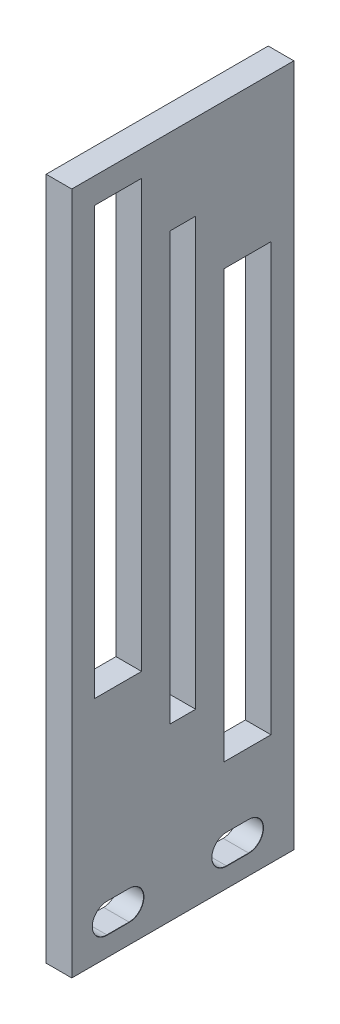
SolidWorks part; units mm, degrees
ref_plane "Front Plane" through (0, 0, 0) normal (0, 0, 1) x (1, 0, 0)
ref_plane "Top Plane" through (0, 0, 0) normal (0, 1, 0) x (1, 0, 0)
ref_plane "Right Plane" through (0, 0, 0) normal (1, 0, 0) x (0, 0, -1)
sketch "Sketch1" plane through (0, 0, 0) normal (1, 0, 0) x (0, 0, -1)
  line L1 (0, 0) -> (26, 0)
  line L2 (0, 0) -> (0, 80)
  line L3 (0, 80) -> (26, 80)
  line L4 (26, 0) -> (26, 80)
  dimension "D1" = 26
  dimension "D2" = 80
extrude "Boss-Extrude1" add sketch "Sketch1" along normal blind 3
sketch "Sketch2" plane through (3, 0, 0) normal (1, 0, 0) x (0, 0, -1)
  line L0 (26, 80) -> (0, 80) construction
  line L1 (2.675, 77) -> (8.175, 77)
  line L2 (2.675, 77) -> (2.675, 27)
  line L3 (2.675, 27) -> (8.175, 27)
  line L4 (8.175, 77) -> (8.175, 27)
  line L5 (11.5, 70) -> (14.5, 70)
  line L6 (11.5, 70) -> (11.5, 20)
  line L7 (11.5, 20) -> (14.5, 20)
  line L8 (14.5, 70) -> (14.5, 20)
  line L9 (17.825, 63) -> (23.325, 63)
  line L10 (17.825, 63) -> (17.825, 13)
  line L11 (17.825, 13) -> (23.325, 13)
  line L12 (23.325, 63) -> (23.325, 13)
  line L13 (0, 80) -> (0, 0) construction
  point P14 (13, 70)
  point P17 (5.425, 77)
  point P18 (20.575, 63)
  dimension "D1" = 50
  dimension "D2" = 50
  dimension "D3" = 50
  dimension "D4" = 5.5
  dimension "D5" = 5.5
  dimension "D6" = 3
  dimension "D7" = 3
  dimension "D8" = 10
  dimension "D9" = 17
  dimension "D10" = 13
  dimension "D11" = 15.15
  dimension "D12" = 7.575
extrude "Cut-Extrude1" cut sketch "Sketch2" against normal blind 3
hole_wizard "M3 Clearance Slot1" positions "Sketch3" profile "Sketch5" size "M3" standard "ANSI Metric" slot yes end condition through all
sketch "Sketch3" plane through (3, 0, 0) normal (1, 0, 0) x (0, 0, -1)
  line L0 (0, 0) -> (26, 0) construction
  line L3 (2.675, 27) -> (8.175, 27) construction
  line L4 (8.425, 4) -> (2.425, 4) construction
  point P0 (5.425, 4)
  point P2 (19.425, 4)
  point P15 (5.425, 27)
  dimension "D1" = 4
  dimension "D2" = 4
  dimension "D3" = 14
  dimension "D4" = 6
sketch "Sketch5" plane through (3, 4, -5.425) normal (0, 1, 0) x (0, 0, -1)
  line L0 (0, 0) -> (0, 3)
  line L1 (0, 3) -> (1.7, 3)
  line L2 (1.7, 3) -> (1.7, 0.025)
  line L3 (1.7, 0.025) -> (1.725, 0)
  line L5 (1.725, 0) -> (0, 0)
  line L6 (-1.7, 0.025) -> (-1.725, 0) construction
  line L11 (0, -6.35) -> (0, 107.95) construction
  dimension "Thru Hole Dia." = 3.4
  dimension "Thru Hole Depth" = 3
  dimension "Near C'Sink Dia." = 3.45
  dimension "Near C'Sink Angle" = 90
equation "\"D10@Sketch2\"=\"D1@Sketch1\"/2"
equation "\"D12@Sketch2\"=(\"D11@Sketch2\")/2"
